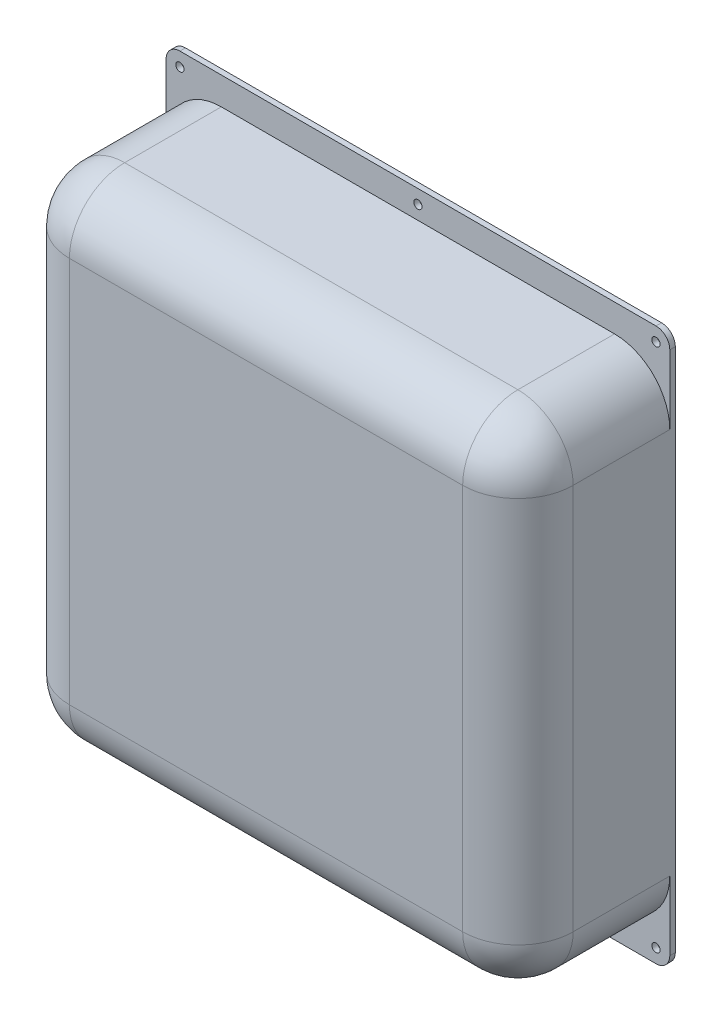
SolidWorks part; units mm, degrees
ref_plane "Front Plane" through (0, 0, 0) normal (0, 0, 1) x (1, 0, 0)
ref_plane "Top Plane" through (0, 0, 0) normal (0, 1, 0) x (1, 0, 0)
ref_plane "Right Plane" through (0, 0, 0) normal (1, 0, 0) x (0, 0, -1)
sketch "Sketch1" plane through (0, 0, 0) normal (0, 0, 1) x (1, 0, 0)
  line L1 (86.195, 100) -> (-86.195, 100)
  line L2 (91.195, 95) -> (91.195, -95)
  line L3 (86.195, -100) -> (-86.195, -100)
  line L4 (-91.195, 95) -> (-91.195, -95)
  circle A0 centre (86.195, -95) radius 1.5 construction
  circle A1 centre (0, -95) radius 1.5 construction
  circle A2 centre (-86.195, -95) radius 1.5 construction
  circle A3 centre (-86.195, 95) radius 1.5 construction
  circle A4 centre (0, 95) radius 1.5 construction
  circle A5 centre (86.195, 95) radius 1.5 construction
  circle A6 centre (86.195, -95) radius 1.5
  circle A7 centre (0, -95) radius 1.5
  circle A8 centre (-86.195, -95) radius 1.5
  circle A9 centre (-86.195, 95) radius 1.5
  circle A10 centre (0, 95) radius 1.5
  circle A11 centre (86.195, 95) radius 1.5
  arc A12 (91.195, -95) -> (86.195, -100) centre (86.195, -95) cw
  arc A13 (86.195, 100) -> (91.195, 95) centre (86.195, 95) cw
  arc A14 (-86.195, 100) -> (-91.195, 95) centre (-86.195, 95) ccw
  arc A15 (-86.195, -100) -> (-91.195, -95) centre (-86.195, -95) cw
  dimension "D5" = 5
  dimension "D1" = 5
  dimension "D2" = 5
  dimension "D3" = 5
  dimension "D4" = 5
extrude "Boss-Extrude1" add sketch "Sketch1" along normal blind 2
sketch "Sketch2" plane through (0, 0, 2) normal (0, 0, 1) x (1, 0, 0)
  line L0 (91.195, -95) -> (91.195, 95) construction
  line L1 (91.195, -90) -> (-91.195, -90)
  line L2 (91.195, -90) -> (91.195, 90)
  line L3 (91.195, 90) -> (-91.195, 90)
  line L4 (-91.195, -90) -> (-91.195, 90)
  line L5 (-91.195, 95) -> (-91.195, -95) construction
  line L6 (-86.195, -100) -> (86.195, -100) construction
  line L7 (86.195, 100) -> (-86.195, 100) construction
  dimension "D1" = 10
  dimension "D2" = 10
extrude "Boss-Extrude2" add sketch "Sketch2" along normal blind 55
fillet "Fillet1" radius 20 8 edges at (-91.195, -90, 29.5) (91.195, -90, 29.5) (-91.195, 90, 29.5) (-91.195, 0, 57) (91.195, 0, 57) (91.195, 90, 29.5) (0, 90, 57) (0, -90, 57)
shell "Shell1" thickness 2 removed face at (1.5, 95, 0)
